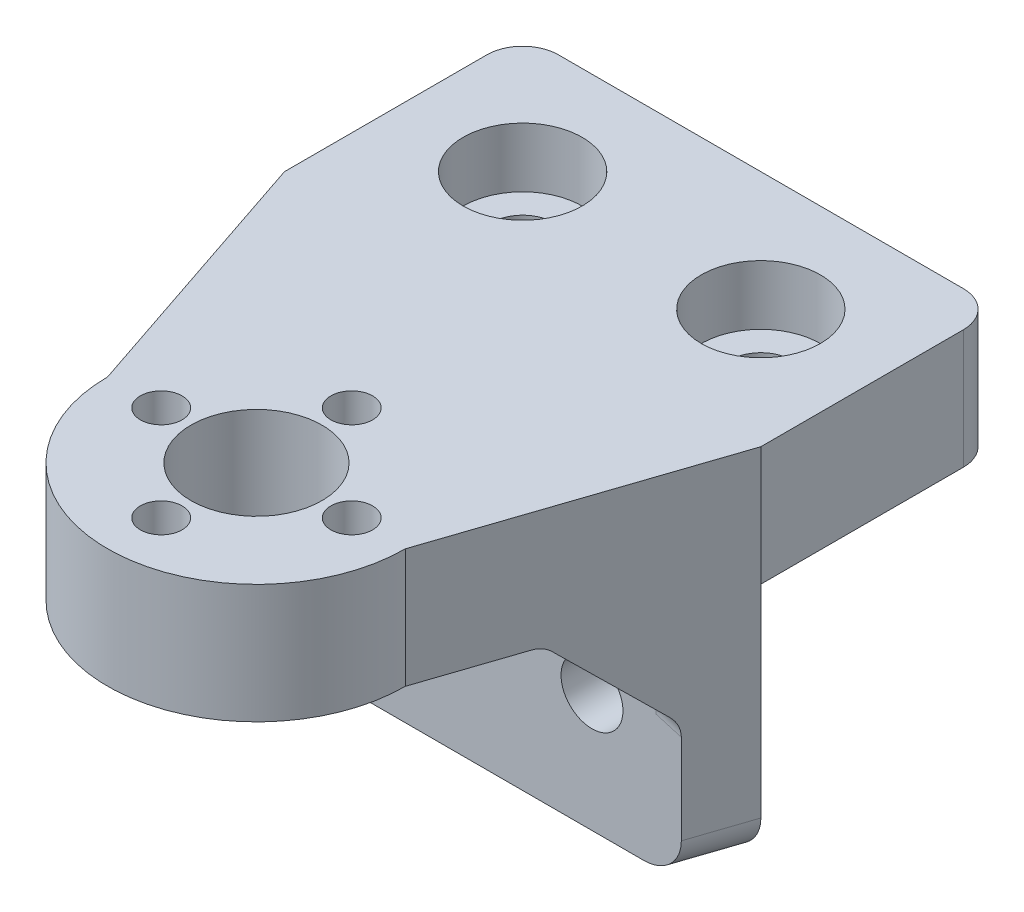
SolidWorks part; units mm, degrees
material "PET"
ref_plane "Front Plane" through (0, 0, 0) normal (0, 0, 1) x (1, 0, 0)
ref_plane "Top Plane" through (0, 0, 0) normal (0, 1, 0) x (1, 0, 0)
ref_plane "Right Plane" through (0, 0, 0) normal (1, 0, 0) x (0, 0, -1)
sketch "Sketch1" plane through (0, 0, 0) normal (0, 1, 0) x (1, 0, 0)
  circle A0 centre (0, 0) radius 12.5
  circle A1 centre (0, 0) radius 5.5
  circle A2 centre (0, 0) radius 8 construction
  circle A3 centre (0, 8) radius 1.75
  circle A4 centre (8, 0) radius 1.75
  circle A5 centre (0, -8) radius 1.75
  circle A6 centre (-8, 0) radius 1.75
  point P16 (0, 0)
  dimension "D1" = 25
  dimension "D2" = 11
  dimension "D3" = 16
  dimension "D4" = 3.5
  dimension "D5" = 4
extrude "Boss-Extrude1" add sketch "Sketch1" along normal blind 10
sketch "Sketch3" plane through (0, 0, 0) normal (0, 1, 0) x (1, 0, 0)
  line L0 (-20, 32.35) -> (20, 32.35) construction
  line L1 (-20, 22.35) -> (20, 22.35) construction
  line L2 (-12.5, 0) -> (-20, 22.35)
  line L3 (-20, 22.35) -> (20, 22.35) construction
  line L4 (12.5, 0) -> (20, 22.35)
  line L5 (-20, 22.35) -> (-20, 42.35)
  line L6 (-20, 42.35) -> (20, 42.35)
  line L7 (20, 22.35) -> (20, 42.35)
  line L8 (0, 0) -> (0, 57.3355) construction
  line L9 (-18.3221, 17.35) -> (18.3221, 17.35) construction
  arc A0 (12.5, 0) -> (-12.5, 0) centre (0, 0) ccw
  circle A1 centre (-10, 32.35) radius 2.6
  circle A2 centre (10, 32.35) radius 2.6
  point P11 (0, 42.35)
  point P16 (0, 0)
  dimension "D1" = 25
  dimension "D2" = 22.35
  dimension "D3" = 20
  dimension "D4" = 5.2
  dimension "D6" = 40
  dimension "D5" = 5.2
  dimension "D7" = 10
  dimension "D8" = 10
  dimension "D9" = 5
extrude "Boss-Extrude2" add sketch "Sketch3" along normal blind 10
sketch "Sketch4" plane through (0, 0, 0) normal (0, 1, 0) x (1, 0, 0)
  line L0 (-20, 32.35) -> (20, 32.35) construction
  line L1 (-20, 22.35) -> (20, 22.35)
  line L2 (-12.5, 0) -> (-20, 22.35)
  line L3 (-20, 22.35) -> (20, 22.35) construction
  line L4 (12.5, 0) -> (20, 22.35)
  line L5 (-20, 22.35) -> (-20, 42.35)
  line L6 (-20, 42.35) -> (20, 42.35)
  line L7 (20, 22.35) -> (20, 42.35)
  line L8 (0, 0) -> (0, 57.3355) construction
  line L9 (-18.3221, 17.35) -> (18.3221, 17.35)
  arc A0 (12.5, 0) -> (-12.5, 0) centre (0, 0) ccw
  circle A1 centre (-10, 32.35) radius 2.6
  circle A2 centre (10, 32.35) radius 2.6
  point P11 (0, 42.35)
  point P16 (0, 0)
  dimension "D1" = 25
  dimension "D2" = 22.35
  dimension "D3" = 20
  dimension "D4" = 5.2
  dimension "D6" = 40
  dimension "D5" = 5.2
  dimension "D7" = 10
  dimension "D8" = 10
  dimension "D9" = 5
extrude "Boss-Extrude3" add sketch "Sketch4" against normal blind 20 contours L2 L9 L4 L1 region at (0, 0, -19.8865)
sketch "Sketch5" plane through (0, 0, -17.35) normal (0, 0, 1) x (1, 0, 0)
  line L0 (-18.3221, -10) -> (18.3221, -10) construction
  line L1 (-18.3221, -20) -> (-18.3221, 0) construction
  line L2 (18.3221, -20) -> (18.3221, 0) construction
  circle A0 centre (-10.8221, -10) radius 2.6
  circle A1 centre (10.8221, -10) radius 2.6
  point P10 (0, 0)
  point P11 (0, 0)
  point P12 (0, 0)
  dimension "D1" = 5.2
  dimension "D2" = 5.2
  dimension "D3" = 7.5
  dimension "D4" = 7.5
extrude "Cut-Extrude1" cut sketch "Sketch5" against normal through all
fillet "Fillet3" radius 3 2 edges at (19.1611, -20, -19.85) (-19.1611, -20, -19.85)
fillet "Fillet4" radius 3 2 edges at (20, 5, -42.35) (-20, 5, -42.35)
sketch "Sketch6" plane through (-11.2349, 0, 3.7701) normal (-0.948, 0, 0.3181) x (0.3181, 0, 0.948)
  line L0 (-22.2775, -8.5) -> (-13.1271, 0)
  line L1 (-22.2775, -17) -> (-22.2775, 0) construction
  line L2 (-22.2775, 0) -> (-3.9767, 0) construction
  point P6 (-22.2775, -17)
  point P7 (-3.9767, 0)
  point P9 (0, 0)
  point P10 (-6.9873, 0)
  point P11 (-22.2775, -17)
  point P12 (-22.2775, -17)
  point P13 (-22.2775, -8.5)
  point P14 (-13.1271, 0)
rib "Rib1" sketch "Sketch6" sketch "Sketch6" thickness 2 extrusion direction parallel to sketch draft on no parameters "D1"=2
fillet "Fillet6" radius 2 2 edges at (-17.2673, -8.1883, -17.35) (-14.463, 0, -8.9931)
sketch "Sketch7" plane through (11.2349, 0, 3.7701) normal (0.948, 0, 0.3181) x (0.3181, 0, -0.948)
  line L0 (22.2775, -8.5) -> (13.1271, 0)
  line L1 (22.2775, -17) -> (22.2775, 0) construction
  line L2 (3.9767, 0) -> (22.2775, 0) construction
rib "Rib2" sketch "Sketch7" sketch "Sketch7" thickness 2 extrusion direction parallel to sketch draft on no parameters "D1"=2
fillet "Fillet7" radius 2 2 edges at (17.2673, -8.1883, -17.35) (14.463, 0, -8.9931)
sketch "Sketch8" plane through (0, 10, 0) normal (0, 1, 0) x (1, 0, 0)
  circle A0 centre (-10, 32.35) radius 5
  circle A1 centre (10, 32.35) radius 5
  dimension "D1" = 10
  dimension "D2" = 10
extrude "Cut-Extrude2" cut sketch "Sketch8" against normal blind 5
